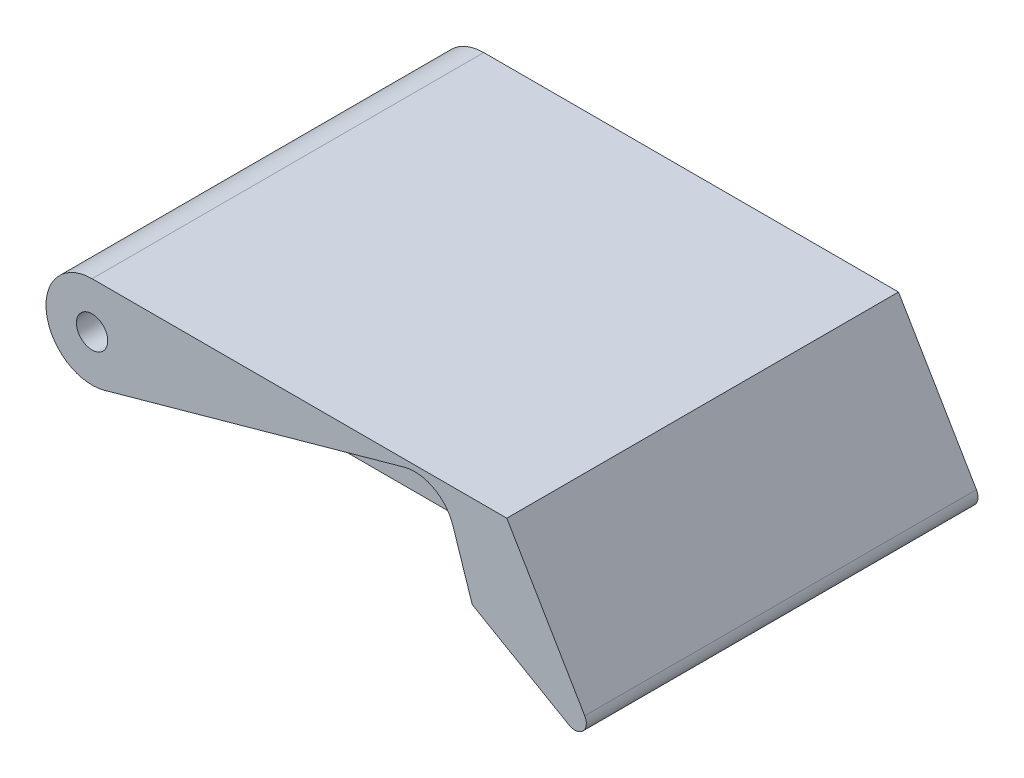
SolidWorks part; units mm, degrees
ref_plane "Front Plane" through (0, 0, 0) normal (0, 0, 1) x (1, 0, 0)
ref_plane "Top Plane" through (0, 0, 0) normal (0, 1, 0) x (1, 0, 0)
ref_plane "Right Plane" through (0, 0, 0) normal (1, 0, 0) x (0, 0, -1)
sketch "Sketch1" plane through (0, 0, 0) normal (0, 0, 1) x (1, 0, 0)
  line L0 (0, 6.35) -> (57.15, 6.35)
  line L3 (70.9475, -17.0656) -> (52.3875, -6.35)
  line L4 (52.3875, -6.35) -> (0, -6.35)
  line L5 (57.15, 6.35) -> (70.9475, -17.0656)
  arc A0 (0, 6.35) -> (0, -6.35) centre (0, 0) ccw
  point P0 (0, 0)
  dimension "D1" = 150
  dimension "D2" = 52.3875
  dimension "D4" = 21.4312
  dimension "D6" = 57.15
  dimension "D7" = 12.7
extrude "Boss-Extrude1" add sketch "Sketch1" along normal mid plane 53.975
sketch "Sketch2" plane through (0, 0, 26.9875) normal (0, 0, 1) x (1, 0, 0)
  line L1 (57.15, 6.35) -> (0, 6.35) construction
  circle A0 centre (0, 0) radius 2.159
  circle A1 centre (44.45, 0) radius 1.905
  dimension "D4" = 4.318
  dimension "D5" = 3.81
  dimension "D1" = 44.45
  dimension "D3" = 6.35
extrude "Cut-Extrude1" cut sketch "Sketch2" against normal through all
sketch "Sketch3" plane through (0, 0, 26.9875) normal (0, 0, 1) x (1, 0, 0)
  line L4 (1.7009, -6.118) -> (42.9617, 5.3532)
  line L7 (49.7281, 1.7359) -> (52.3875, -6.35)
  line L12 (0, -6.35) -> (52.3875, -6.35) construction
  line L13 (52.3875, -6.35) -> (0, -6.35)
  arc A4 (0, -6.35) -> (1.7009, -6.118) centre (0, 0) ccw
  arc A13 (49.7281, 1.7359) -> (42.9617, 5.3532) centre (44.45, 0) ccw
  dimension "D1" = 5.5563
extrude "Cut-Extrude2" cut sketch "Sketch3" against normal blind 9.525
mirror "Mirror1" about plane through (0, 0, 0) normal (0, 0, 1) of "Cut-Extrude2"
fillet "Fillet1" radius 1.5875 1 edges at (70.9475, -17.0656, 0)
